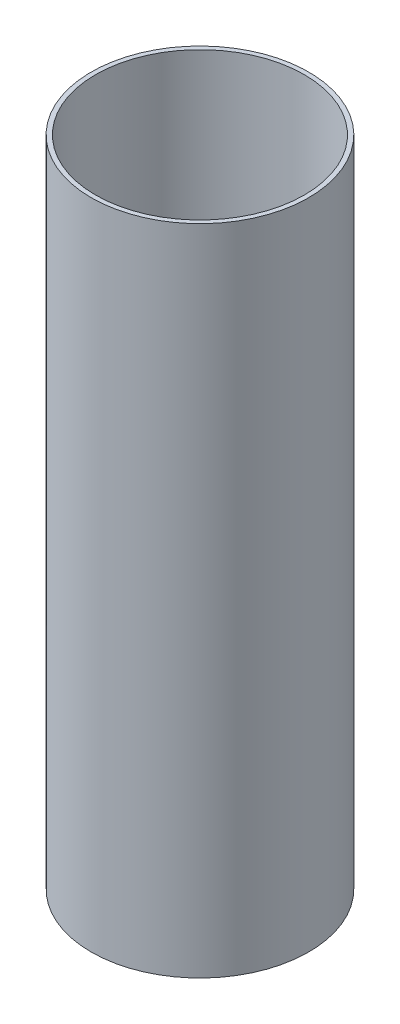
SolidWorks part; units mm, degrees
material "G12 Fiberglass"
ref_plane "Front Plane" through (0, 0, 0) normal (0, 0, 1) x (1, 0, 0)
ref_plane "Top Plane" through (0, 0, 0) normal (0, 1, 0) x (1, 0, 0)
ref_plane "Right Plane" through (0, 0, 0) normal (1, 0, 0) x (0, 0, -1)
ref_axis "Axis1" through (0, 55, 0) along (0, -1, 0)
sketch "Sketch1" plane through (0, 0, 0) normal (0, 1, 0) x (1, 0, 0)
  circle A0 centre (0, 0) radius 36.5125
  circle A1 centre (0, 0) radius 38.0746
  dimension "D1" = 73.025
  dimension "D2" = 76.1492
extrude "Boss-Extrude1" add sketch "Sketch1" along normal blind 228.6
ref_plane "Midplane" through (0, 114.3, 0) normal (0, 1, 0) x (1, 0, 0)
